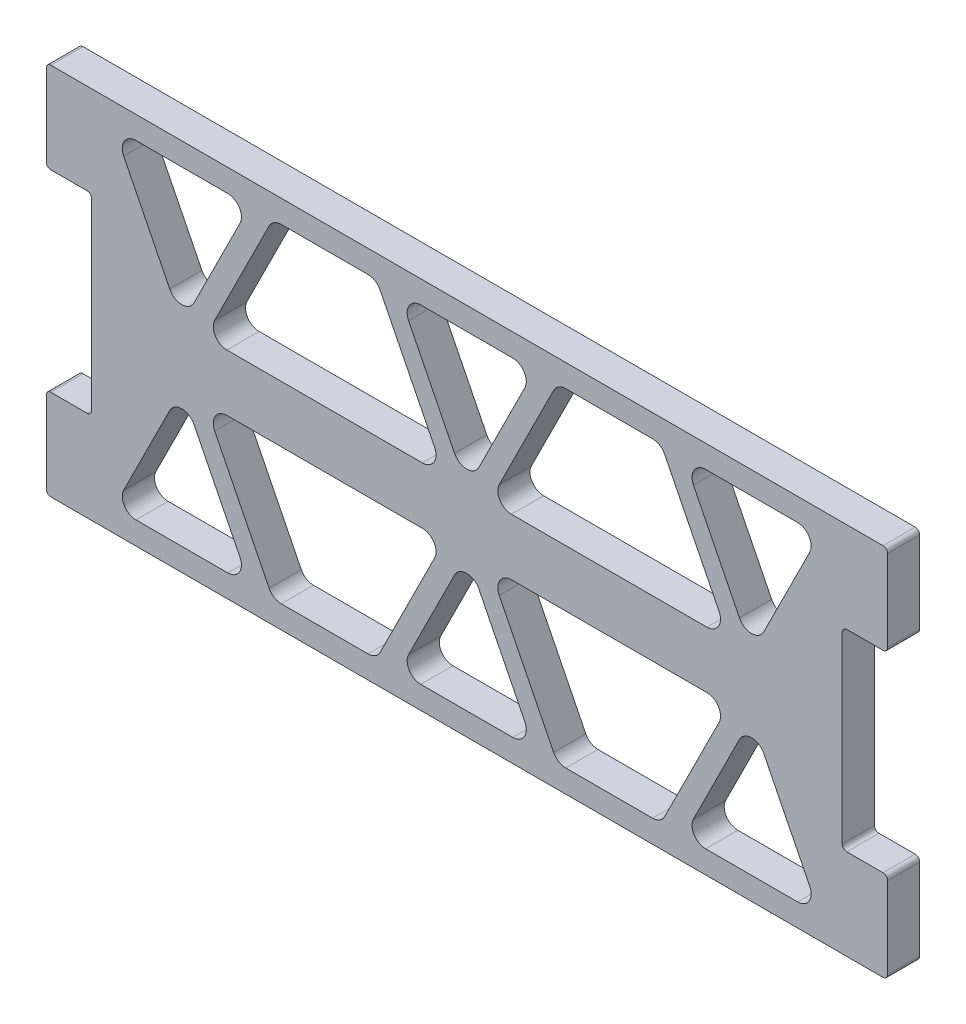
SolidWorks part; units mm, degrees
ref_plane "Front" through (0, 0, 0) normal (0, 0, 1) x (1, 0, 0)
ref_plane "Top" through (0, 0, 0) normal (0, 1, 0) x (1, 0, 0)
ref_plane "Right" through (0, 0, 0) normal (1, 0, 0) x (0, 0, -1)
sketch "Sketch1" plane through (0, 0, 0) normal (0, 0, 1) x (1, 0, 0)
  line L1 (52.5907, -34.1605) -> (-52.5907, -34.1605)
  line L2 (52.5907, -34.1605) -> (52.5907, 34.1605)
  line L3 (52.5907, 34.1605) -> (-52.5907, 34.1605)
  line L4 (-52.5907, -34.1605) -> (-52.5907, 34.1605)
  line L5 (52.5907, -34.1605) -> (-52.5907, 34.1605) construction
  line L6 (52.5907, 34.1605) -> (-52.5907, -34.1605) construction
  point P0 (0, 0)
  dimension "D1" = 105.1814
extrude "Boss-Extrude1" add sketch "Sketch1" along normal blind 4.5085
sketch "Sketch2" plane through (0, 0, 4.5085) normal (0, 0, 1) x (1, 0, 0)
  line L0 (52.5907, -34.1605) -> (52.5907, 34.1605) construction
  line L1 (-52.5907, 34.1605) -> (52.5907, 34.1605)
  line L2 (-52.5907, 34.1605) -> (-52.5907, 18.227)
  line L3 (-52.5907, 18.227) -> (52.5907, 18.227)
  line L4 (52.5907, 34.1605) -> (52.5907, 18.227)
  dimension "D1" = 15.9335
extrude "Cut-Extrude1" cut sketch "Sketch2" against normal blind 10.795
sketch "Sketch3" plane through (0, 0, 4.5085) normal (0, 0, 1) x (1, 0, 0)
  line L0 (-52.5907, 18.227) -> (-52.5907, -34.1605) construction
  line L1 (-52.5907, -34.1605) -> (-58.9407, -34.1605)
  line L2 (-52.5907, -34.1605) -> (-52.5907, -21.4605)
  line L3 (-52.5907, -21.4605) -> (-58.9407, -21.4605)
  line L4 (-58.9407, -34.1605) -> (-58.9407, -21.4605)
  line L5 (-52.5907, 18.227) -> (-58.9407, 18.227)
  line L6 (-52.5907, 18.227) -> (-52.5907, 5.527)
  line L7 (-52.5907, 5.527) -> (-58.9407, 5.527)
  line L8 (-58.9407, 18.227) -> (-58.9407, 5.527)
  dimension "D1" = 6.35
  dimension "D2" = 12.7
  dimension "D3" = 39.6875
  dimension "D4" = 12.7
  dimension "D5" = 6.35
extrude "Boss-Extrude2" add sketch "Sketch3" against normal blind 4.5085
mirror "Mirror1" about plane through (0, 0, 0) normal (1, 0, 0) of "Boss-Extrude2"
fillet "Fillet1" radius 0.635 12 edges at (58.9407, 18.227, 2.2542) (58.9407, 5.527, 2.2542) (52.5907, 5.527, 2.2542) (52.5907, -21.4605, 2.2542) (58.9407, -21.4605, 2.2542) (58.9407, -34.1605, 2.2542) (-52.5907, 5.527, 2.2542) (-52.5907, -21.4605, 2.2542) (-58.9407, -34.1605, 2.2542) (-58.9407, 5.527, 2.2542) (-58.9407, 18.227, 2.2542) (-58.9407, -21.4605, 2.2542)
sketch "Sketch4" plane through (0, 0, 0) normal (0, 0, -1) x (-1, 0, 0)
  line L0 (-49.4157, 15.052) -> (-30.3657, 15.052)
  line L1 (-30.3657, 15.052) -> (-39.8907, -3.998)
  line L2 (-39.8907, -3.998) -> (-49.4157, 15.052)
  line L3 (58.3057, 18.227) -> (-58.3057, 18.227) construction
  line L4 (-52.5907, -20.8255) -> (-52.5907, 4.892) construction
  point P5 (0, 0)
  point P7 (-40.3383, -8.514)
  dimension "D1" = 19.05
  dimension "D2" = 3.175
  dimension "D3" = 9.525
  dimension "D4" = 19.05
  dimension "D5" = 3.175
extrude "Cut-Extrude2" cut sketch "Sketch4" against normal blind 4.7625
pattern_linear "LPattern1" count 3 spacing 39.9161 along (-1, 0, 0) of "Cut-Extrude2"
sketch "Sketch5" plane through (0, 0, 0) normal (0, 0, -1) x (-1, 0, 0)
  line L0 (-27.1907, 15.052) -> (-12.6746, 15.052)
  line L1 (-12.6746, 15.052) -> (-3.1496, -3.998)
  line L2 (-3.1496, -3.998) -> (-36.7157, -3.998)
  line L3 (-36.7157, -3.998) -> (-27.1907, 15.052)
  line L4 (9.5504, 15.052) -> (-9.4996, 15.052) construction
  dimension "D1" = 3.175
  dimension "D2" = 3.175
  dimension "D3" = 0
  dimension "D4" = 0
  dimension "D5" = 3.175
  dimension "D6" = 3.175
extrude "Cut-Extrude3" cut sketch "Sketch5" against normal blind 4.7625
mirror "Mirror2" about plane through (0, 0, 0) normal (1, 0, 0) of "Cut-Extrude3"
fillet "Fillet2" radius 1.905 9 edges at (-49.4666, 15.052, 2.2542) (-39.9416, -3.998, 2.2542) (-30.4166, 15.052, 2.2542) (-9.5504, 15.052, 2.2542) (9.4996, 15.052, 2.2542) (30.3657, 15.052, 2.2542) (-0.0254, -3.998, 2.2542) (39.8907, -3.998, 2.2542) (49.4157, 15.052, 2.2542)
ref_plane "Plane1" through (0, -7.9667, 0) normal (0, 1, 0) x (1, 0, 0)
mirror "Mirror3" about plane through (0, -7.9667, 0) normal (0, 1, 0) of "LPattern1", "Mirror2"
fillet "Fillet3" radius 1.905 25 edges at (3.1496, -11.9355, 2.2542) (36.7157, -11.9355, 2.2542) (39.8907, -11.9355, 2.2542) (30.3657, -30.9855, 2.2542) (12.6746, -30.9855, 2.2542) (49.4157, -30.9855, 2.2542) (27.1907, -30.9855, 2.2542) (9.4996, -30.9855, 2.2542) (-0.0254, -11.9355, 2.2542) (-9.5504, -30.9855, 2.2542) (-49.4666, -30.9855, 2.2542) (-30.4166, -30.9855, 2.2542) (-39.9416, -11.9355, 2.2542) (-3.1496, -11.9355, 2.2542) (-12.6746, -30.9855, 2.2542) (-27.1907, -30.9855, 2.2542) (-36.7157, -11.9355, 2.2542) (-36.7157, -3.998, 2.2542) (-3.1496, -3.998, 2.2542) (-27.1907, 15.052, 2.2542) (-12.6746, 15.052, 2.2542) (27.1907, 15.052, 2.2542) (12.6746, 15.052, 2.2542) (3.1496, -3.998, 2.2542) (36.7157, -3.998, 2.2542)
